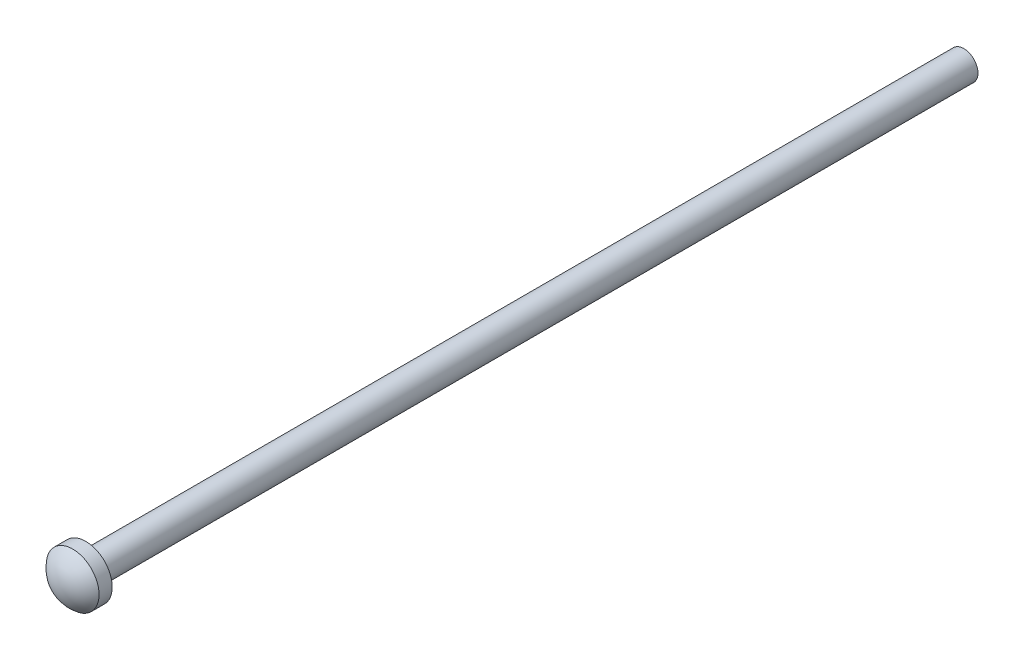
SolidWorks part; units mm, degrees
material "Plain Carbon Steel"
ref_plane "Front Plane" through (0, 0, 0) normal (0, 0, 1) x (1, 0, 0)
ref_plane "Top Plane" through (0, 0, 0) normal (0, 1, 0) x (1, 0, 0)
ref_plane "Right Plane" through (0, 0, 0) normal (1, 0, 0) x (0, 0, -1)
sketch "Sketch1" plane through (0, 0, 0) normal (0, 0, 1) x (1, 0, 0)
  circle A2 centre (0, 60) radius 3.25
  circle A3 centre (0, 60) radius 3.25
  dimension "D1" = 0.25
sketch "Sketch2" plane through (0, 0, 0) normal (1, 0, 0) x (0, 0, -1)
  line L0 (0, 0) -> (200, 0) construction
  line L1 (0, 0) -> (200, 0)
sweep "Sweep1" add profiles "Sketch1" path "Sketch2"
sketch "Sketch3" plane through (0, 0, 0) normal (0, 0, 1) x (1, 0, 0)
  circle A0 centre (0, 60) radius 6
extrude "Boss-Extrude1" add sketch "Sketch3" along normal blind 3
dome "Dome1" faces to dome 1 distance 3 reverse direction no elliptical dome no face at (6, 60, 3) parameters "D1"=3
